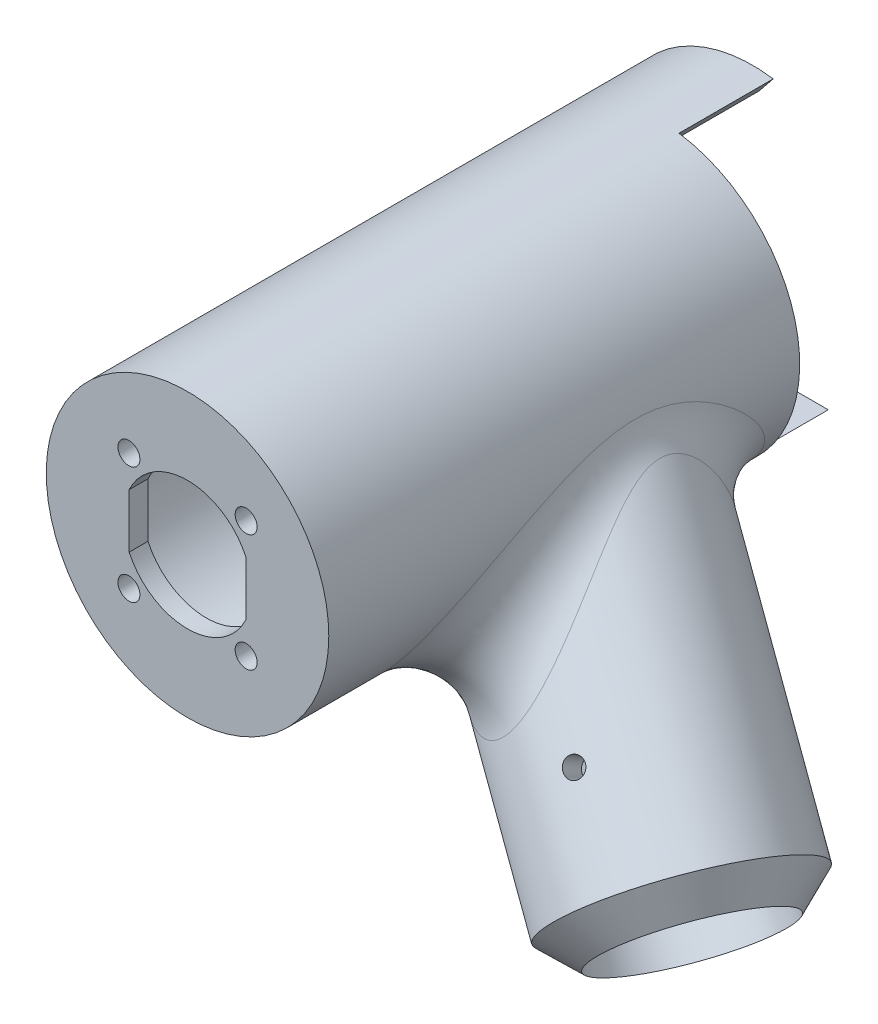
SolidWorks part; units mm, degrees
material "ABS"
ref_plane "Front Plane" through (0, 0, 0) normal (0, 0, 1) x (1, 0, 0)
ref_plane "Top Plane" through (0, 0, 0) normal (0, 1, 0) x (1, 0, 0)
ref_plane "Right Plane" through (0, 0, 0) normal (1, 0, 0) x (0, 0, -1)
sketch "Sketch1" plane through (0, 0, 0) normal (0, 0, 1) x (1, 0, 0)
  circle A0 centre (0, 0) radius 22.5
  dimension "D1" = 45
extrude "Boss-Extrude1" add sketch "Sketch1" along normal blind 90
sketch "Sketch2" plane through (0, 0, 0) normal (0, 0, -1) x (-1, 0, 0)
  circle A0 centre (0, 0) radius 16.3
  circle A1 centre (0, 0) radius 22.5 construction
  dimension "D1" = 6.2
extrude "Cut-Extrude1" cut sketch "Sketch2" against normal offset from surface (87 mm away) 3 up to face at (22.5, 0, 90)
sketch "Sketch3" plane through (0, 0, 0) normal (1, 0, 0) x (0, 0, -1)
  line L1 (15, -19) -> (-15, -19)
  line L2 (15, -19) -> (15, 19)
  line L3 (15, 19) -> (-15, 19)
  line L4 (-15, -19) -> (-15, 19)
  line L5 (15, -19) -> (-15, 19) construction
  line L6 (15, 19) -> (-15, -19) construction
  point P0 (0, 0)
  dimension "D1" = 15
  dimension "D2" = 38
extrude "Cut-Extrude2" cut sketch "Sketch3" along normal blind 33
sketch "Sketch4" plane through (0, 0, 0) normal (1, 0, 0) x (0, 0, -1)
  line L0 (0, 0) -> (-40, 0) construction
  line L1 (0, -22.5) -> (0, 22.5) construction
  line L2 (-10, 15) -> (-60, 15)
  line L3 (-10, 15) -> (-10, -15)
  line L4 (-10, -15) -> (-60, -15)
  line L5 (-60, 15) -> (-60, -15)
  line L6 (-10, 15) -> (-60, -15) construction
  line L7 (-10, -15) -> (-60, 15) construction
  point P2 (-35, 0)
  dimension "D1" = 50
  dimension "D2" = 10
  dimension "D3" = 30
ref_plane "Plane2" through (0, 0, 35) normal (0, 0, -1) x (-1, 0, 0)
sketch3d "3DSketch1"
  line L0 (0, 0, 35) -> (120, -120, 90)
sketch "Sketch5" plane through (0, 0, 35) normal (0, 0, -1) x (-1, 0, 0)
  line L0 (0, 0) -> (-54.3806, -54.3806)
  line L1 (0, 15) -> (0, -15) construction
  dimension "D1" = 45
ref_plane "Plane3" through (0, 0, 35) normal (0.6727, -0.6727, 0.3083) x (0.218, -0.218, -0.9513)
sketch "Sketch6" plane through (0, 0, 35) normal (0.6727, -0.6727, 0.3083) x (0.218, -0.218, -0.9513)
  circle A0 centre (0, 0) radius 17.5
  dimension "D1" = 35
extrude "Boss-Extrude2" add sketch "Sketch6" along normal blind 70
sketch "Sketch7" plane through (54.3448, -54.3448, 24.908) normal (0.6727, -0.6727, 0.3083) x (0.218, -0.218, -0.9513)
  circle A0 centre (-33.2951, 0) radius 12.9
  dimension "D1" = 25.8
extrude "Cut-Extrude3" cut sketch "Sketch7" against normal blind 50
sketch "Sketch8" plane through (0, 0, 0) normal (0, 0, -1) x (-1, 0, 0)
  circle A0 centre (0, 0) radius 19.5
extrude "Cut-Extrude4" cut sketch "Sketch8" against normal blind 61
fillet "Fillet1" radius 10 1 edges at (22.3843, 2.2789, 41.1361)
chamfer "Chamfer1" distance 5 angle 45 1 edges at (59.4607, -34.712, 56.5812)
ref_plane "Plane4" through (12.052, -19, 15) normal (0.7354, 0.6538, -0.178) x (-0.459, 0.2874, -0.8407)
sketch "Sketch9" plane through (12.052, -19, 15) normal (0.7354, 0.6538, -0.178) x (-0.459, 0.2874, -0.8407)
  line L0 (-55.3018, -12.6166) -> (-46.2319, -4.8898) construction
  line L1 (-43.9531, -25.9379) -> (-66.6504, 0.7047) construction
  line L2 (-5.8225, 29.5355) -> (-141.6207, -86.1531) construction
  circle A0 centre (-41.5998, -0.9437) radius 1.5
  dimension "D1" = 3
  dimension "D2" = 18
extrude "Cut-Extrude5" [suppressed] cut sketch "Sketch9" against normal blind 63
sketch "Sketch10" plane through (0, 0, 61) normal (0, 0, -1) x (-1, 0, 0)
  circle A0 centre (0, 0) radius 16.3 construction
  circle A1 centre (0, 0) radius 19.5
  circle A2 centre (0, 0) radius 19.5
  circle A3 centre (0, 0) radius 16.3
  dimension "D1" = 0
extrude "Boss-Extrude4" add sketch "Sketch10" along direction (0, 0, 1) on the side of the normal offset from surface (36 mm away) 25 up to face at (-6.3901, 0, 0)
sketch "Sketch11" plane through (0, 0, 87) normal (0, 0, -1) x (-1, 0, 0)
  line L0 (-9.3, -4.3096) -> (-9.3, 4.3096)
  line L1 (0, -10.25) -> (0, 13.1651) construction
  line L2 (9.3, -4.3096) -> (9.3, 4.3096)
  arc A0 (-9.3, -4.3096) -> (9.3, -4.3096) centre (0, 0) ccw
  arc A1 (9.3, 4.3096) -> (-9.3, 4.3096) centre (0, 0) ccw
  circle A2 centre (0, 13.2) radius 1.75
  circle A3 centre (9.3338, 9.3338) radius 1.75
  circle A4 centre (13.2, 0) radius 1.75
  circle A5 centre (9.3338, -9.3338) radius 1.75
  circle A6 centre (0, -13.2) radius 1.75
  circle A7 centre (-9.3338, -9.3338) radius 1.75
  circle A8 centre (-13.2, 0) radius 1.75
  circle A9 centre (-9.3338, 9.3338) radius 1.75
  dimension "D1" = 20.5
  dimension "D3" = 3.5
  dimension "D2" = 9.3
  dimension "D4" = 13.2
  dimension "D5" = 8
extrude "Cut-Extrude6" cut sketch "Sketch11" against normal blind 20.5 contours A7 | L0 A1 L2 A0 | A5 | A3 | A9 region at (9.3338, -9.3338, 87)
pattern_circular "CirPattern1" [suppressed] count 3 over 360 reverse direction yes of bodies 118
ref_plane "Plane5" through (54.0757, -54.0757, 24.7847) normal (0.6727, -0.6727, 0.3083) x (0.218, -0.218, -0.9513)
sketch "Sketch12" plane through (54.0757, -54.0757, 24.7847) normal (0.6727, -0.6727, 0.3083) x (0.218, -0.218, -0.9513)
  line L0 (-46.1951, 0) -> (-12.0884, 0) construction
  circle A0 centre (-33.2951, 0) radius 12.9 construction
ref_axis "Axis1" through (26.0047, -26.0047, 46.9188) along (0.6727, -0.6727, 0.3083)
ref_plane "Plane6" through (0, 0, 0) normal (-0.7071, -0.7071, 0) x (-0.7071, 0.7071, 0)
sketch "Sketch14" plane through (0, 0, 0) normal (-0.7071, -0.7071, 0) x (-0.7071, 0.7071, 0)
  line L0 (0, -35) -> (-169.7056, -90) construction
  line L1 (-62.2325, -68.7295) -> (-72.7477, -36.2843) construction
  circle A0 centre (-47.1839, -50.2919) radius 1.5
  dimension "D1" = 3
  dimension "D2" = 20
extrude "Cut-Extrude7" cut sketch "Sketch14" along normal blind 40
pattern_circular "CirPattern2" count 3 over 360 about axis through (13.4532, -13.4532, 41.1661) along (0.6727, -0.6727, 0.3083) of "Cut-Extrude7" reverse direction yes
sketch "Sketch15" plane through (0, 0, 0) normal (0, 0, -1) x (-1, 0, 0)
  line L1 (-4.3875, 19) -> (-12.4484, 19)
  line L2 (-4.3875, 19) -> (-4.3875, 26.4516)
  line L3 (-4.3875, 26.4516) -> (-12.4484, 26.4516)
  line L4 (-12.4484, 19) -> (-12.4484, 26.4516)
extrude "Cut-Extrude8" cut sketch "Sketch15" against normal up to surface (15 mm away) up to face at (14.6099, 0, 15)
chamfer "Chamfer2" distance 5 angle 45 1 edges at (4.3875, 19, 7.5) first distance on face at (4.3875, 20.534, 7.5)
